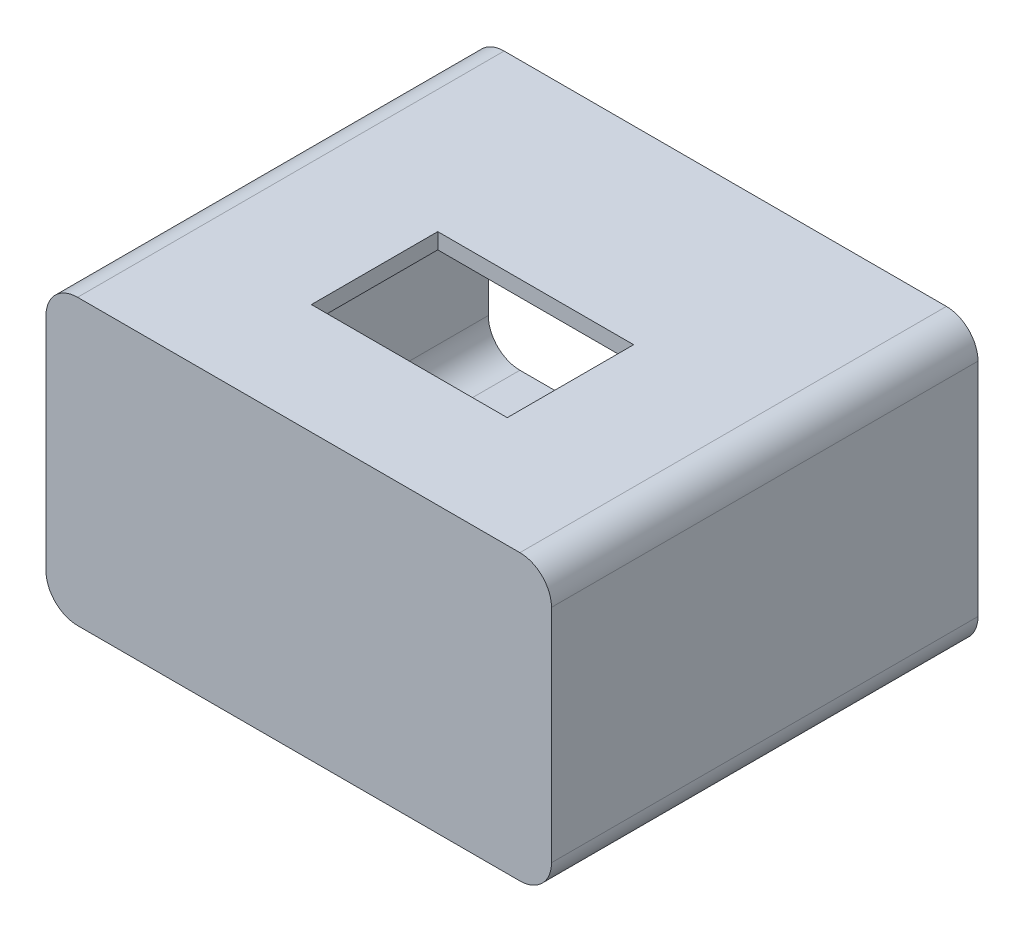
SolidWorks part; units mm, degrees
ref_plane "Front Plane" through (0, 0, 0) normal (0, 0, 1) x (1, 0, 0)
ref_plane "Top Plane" through (0, 0, 0) normal (0, 1, 0) x (1, 0, 0)
ref_plane "Right Plane" through (0, 0, 0) normal (1, 0, 0) x (0, 0, -1)
sketch "Sketch2" plane through (0, 0, 0) normal (0, 0, 1) x (1, 0, 0)
  line L0 (32.5, -20) -> (-32.5, -20) construction
  line L1 (37.5, 15) -> (37.5, -15) construction
  line L2 (-32.5, 20) -> (32.5, 20) construction
  line L3 (-37.5, -15) -> (-37.5, 15) construction
  line L4 (32.5, -20) -> (-32.5, -20)
  line L5 (37.5, 15) -> (37.5, -15)
  line L6 (-32.5, 20) -> (32.5, 20)
  line L7 (-37.5, -15) -> (-37.5, 15)
  line L9 (-35, -22.5) -> (35, -22.5)
  line L10 (-40, -17.5) -> (-40, 17.5)
  line L11 (-35, 22.5) -> (35, 22.5)
  line L12 (40, -17.5) -> (40, 17.5)
  line L13 (-40, -22.5) -> (40, 22.5) construction
  line L14 (-40, 22.5) -> (40, -22.5) construction
  arc A0 (-37.5, -15) -> (-32.5, -20) centre (-32.5, -15) ccw construction
  arc A1 (32.5, -20) -> (37.5, -15) centre (32.5, -15) ccw construction
  arc A2 (37.5, 15) -> (32.5, 20) centre (32.5, 15) ccw construction
  arc A3 (-32.5, 20) -> (-37.5, 15) centre (-32.5, 15) ccw construction
  circle A4 centre (-32.5, -15) radius 1.5 construction
  circle A5 centre (32.5, -15) radius 1.5 construction
  circle A6 centre (32.5, 15) radius 1.5 construction
  circle A7 centre (-32.5, 15) radius 1.5 construction
  arc A8 (-37.5, -15) -> (-32.5, -20) centre (-32.5, -15) ccw
  arc A9 (32.5, -20) -> (37.5, -15) centre (32.5, -15) ccw
  arc A10 (37.5, 15) -> (32.5, 20) centre (32.5, 15) ccw
  arc A11 (-32.5, 20) -> (-37.5, 15) centre (-32.5, 15) ccw
  circle A12 centre (-32.5, -15) radius 1.5
  circle A13 centre (32.5, -15) radius 1.5
  circle A14 centre (32.5, 15) radius 1.5
  circle A15 centre (-32.5, 15) radius 1.5
  arc A16 (35, 22.5) -> (40, 17.5) centre (35, 17.5) cw
  arc A17 (35, -22.5) -> (40, -17.5) centre (35, -17.5) ccw
  arc A18 (-35, -22.5) -> (-40, -17.5) centre (-35, -17.5) cw
  arc A19 (-40, 17.5) -> (-35, 22.5) centre (-35, 17.5) cw
  point P14 (0, 0)
  arc M3 (-32.5, 20) -> (-37.5, 15) centre (-32.5, 15) ccw
  line M4 (-37.5, 15) -> (-37.5, -15)
  arc M5 (-37.5, -15) -> (-32.5, -20) centre (-32.5, -15) ccw
  line M6 (-32.5, -20) -> (32.5, -20)
  arc M7 (32.5, -20) -> (37.5, -15) centre (32.5, -15) ccw
  line M8 (37.5, -15) -> (37.5, 15)
  arc M9 (37.5, 15) -> (32.5, 20) centre (32.5, 15) ccw
  line M10 (32.5, 20) -> (-32.5, 20)
  dimension "D3" = 5
  dimension "D1" = 2.5
  dimension "D2" = 2.5
extrude "Boss-Extrude1" add sketch "Sketch2" along normal blind 65 contours A19 L10 A18 L9 A17 L12 A16 L11 M3 M10 M9 M8 M7 M6 M5 M4 region at (-37.8865, -20.3865, 0)
sketch "Sketch3" plane through (0, 0, 65) normal (0, 0, 1) x (1, 0, 0)
  line L4 (-40, 17.5) -> (-40, -17.5)
  line L5 (-35, -22.5) -> (35, -22.5)
  line L6 (40, -17.5) -> (40, 17.5)
  line L7 (35, 22.5) -> (-35, 22.5)
  line L8 (-40, 17.5) -> (-40, -17.5)
  line L9 (-35, -22.5) -> (35, -22.5)
  line L10 (40, -17.5) -> (40, 17.5)
  line L11 (35, 22.5) -> (-35, 22.5)
  arc A4 (-35, 22.5) -> (-40, 17.5) centre (-35, 17.5) ccw
  arc A5 (-40, -17.5) -> (-35, -22.5) centre (-35, -17.5) ccw
  arc A6 (35, -22.5) -> (40, -17.5) centre (35, -17.5) ccw
  arc A7 (40, 17.5) -> (35, 22.5) centre (35, 17.5) ccw
  arc A8 (-35, 22.5) -> (-40, 17.5) centre (-35, 17.5) ccw
  arc A9 (-40, -17.5) -> (-35, -22.5) centre (-35, -17.5) ccw
  arc A10 (35, -22.5) -> (40, -17.5) centre (35, -17.5) ccw
  arc A11 (40, 17.5) -> (35, 22.5) centre (35, 17.5) ccw
  dimension "D1" = 0
extrude "Boss-Extrude2" add sketch "Sketch3" along normal blind 2.5 contours A8 L8 A9 L9 A10 L10 A11 L11
sketch "Sketch4" plane through (0, 22.5, 0) normal (0, 1, 0) x (1, 0, 0)
  line L0 (-35, 0) -> (35, 0) construction
  line L1 (-15.5, -30) -> (15.5, -30)
  line L2 (-15.5, -30) -> (-15.5, -50)
  line L3 (-15.5, -50) -> (15.5, -50)
  line L4 (15.5, -30) -> (15.5, -50)
  line L5 (-15.5, -30) -> (15.5, -50) construction
  line L6 (-15.5, -50) -> (15.5, -30) construction
  point P0 (0, -40)
  point P5 (0, -38.1052)
  point P8 (0, 0)
  point P9 (0, 0)
  dimension "D1" = 20
  dimension "D2" = 31
  dimension "D3" = 40
extrude "Cut-Extrude1" cut sketch "Sketch4" against normal up to next
